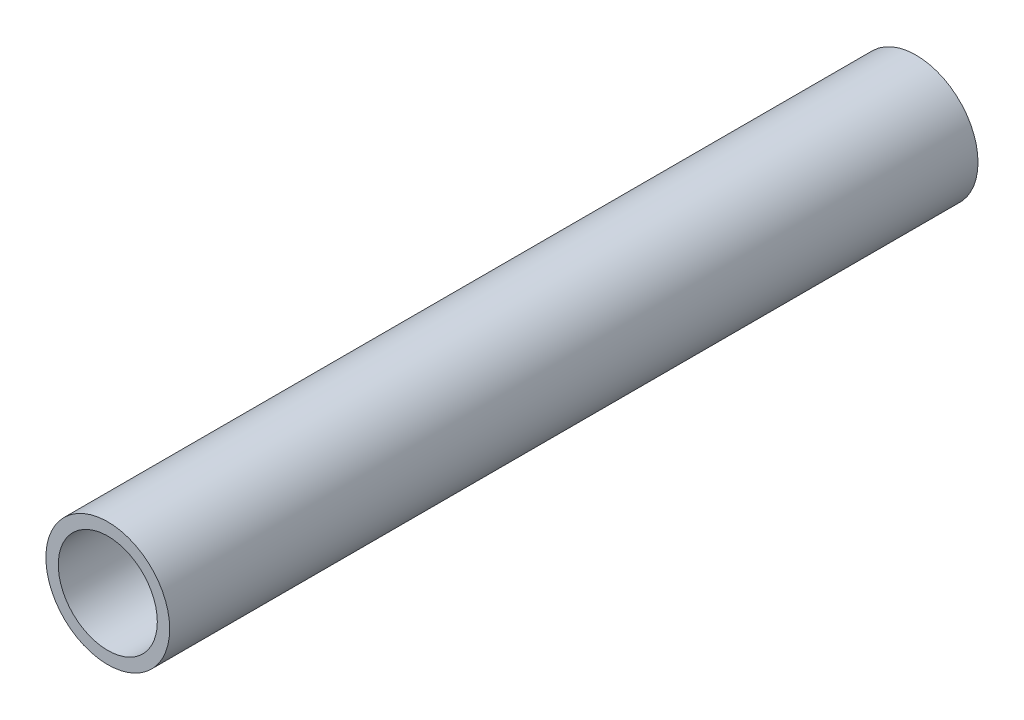
SolidWorks part; units mm, degrees
ref_plane "Front Plane" through (0, 0, 0) normal (0, 0, 1) x (1, 0, 0)
ref_plane "Top Plane" through (0, 0, 0) normal (0, 1, 0) x (1, 0, 0)
ref_plane "Right Plane" through (0, 0, 0) normal (1, 0, 0) x (0, 0, -1)
sketch "Sketch1" plane through (0, 0, 0) normal (0, 0, 1) x (1, 0, 0)
  circle A0 centre (0, 0) radius 1.25
  circle A1 centre (0, 0) radius 1
extrude "Boss-Extrude1" add sketch "Sketch1" along normal blind 16.32
